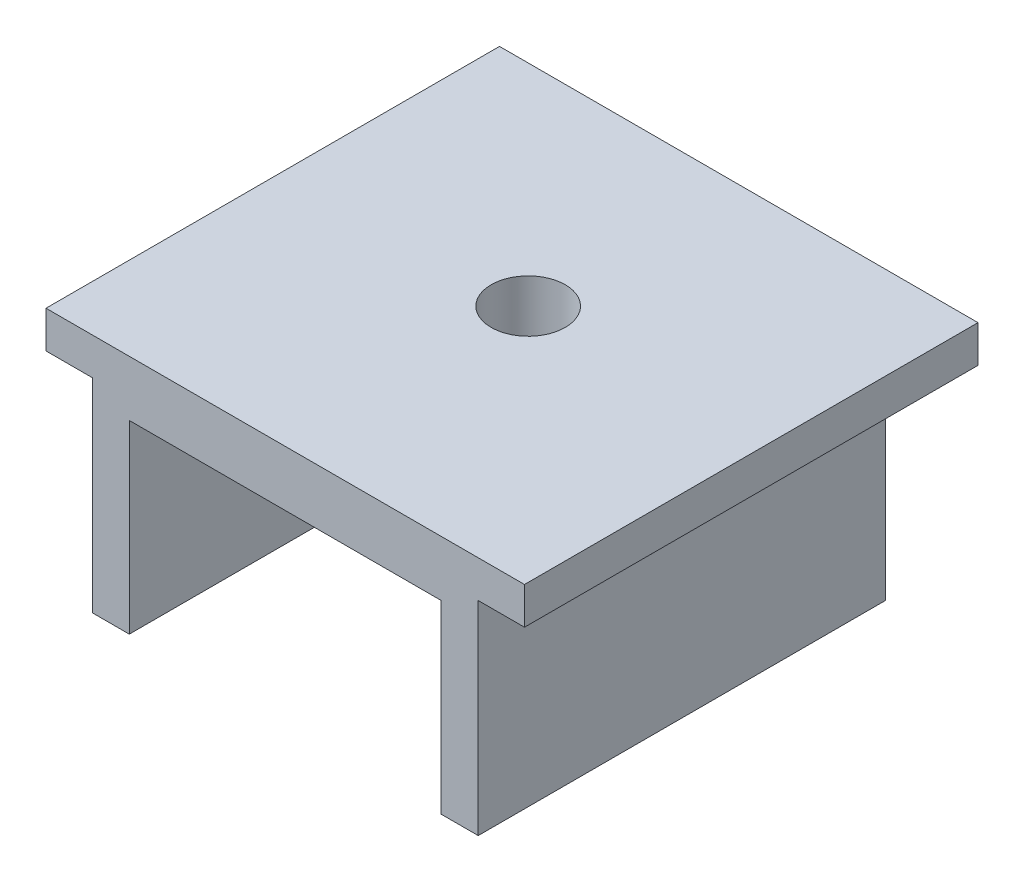
SolidWorks part; units mm, degrees
ref_plane "Front" through (0, 0, 0) normal (0, 0, 1) x (1, 0, 0)
ref_plane "Top" through (0, 0, 0) normal (0, 1, 0) x (1, 0, 0)
ref_plane "Right" through (0, 0, 0) normal (1, 0, 0) x (0, 0, -1)
sketch "草图1" plane through (0, 0, 0) normal (0, 0, 1) x (1, 0, 0)
  line L1 (20.85, -13) -> (-20.85, -13)
  line L2 (20.85, -13) -> (20.85, 13)
  line L3 (20.85, 13) -> (-20.85, 13)
  line L4 (-20.85, -13) -> (-20.85, 13)
  line L5 (20.85, -13) -> (-20.85, 13) construction
  line L6 (20.85, 13) -> (-20.85, -13) construction
  line L7 (-16.85, 7) -> (16.85, 7)
  line L8 (-16.85, 7) -> (-16.85, -13)
  line L9 (-16.85, -13) -> (16.85, -13)
  line L10 (16.85, 7) -> (16.85, -13)
  point P0 (0, 0)
  dimension "D1" = 4
  dimension "D2" = 4
  dimension "D3" = 33.7
  dimension "D4" = 6
  dimension "D5" = 26
extrude "凸台-拉伸1" add sketch "草图1" along normal blind 40 contours L7 L10 L1 L2 L3 L4 L8 region at (18.85, -12.5086, 0)
extrude "凸台-拉伸2" add sketch "草图1<3>" against normal blind 4 contours L10 L7 L8 L1 | L7 L10 L1 L2 L3 L4 L8 region at (18.85, -12.5086, 0) region at (0, -3, 0)
sketch "草图1<3>" plane through (0, 0, 0) normal (0, 0, 1) x (1, 0, 0) same geometry as "草图1"
sketch "草图2" plane through (0, 13, 0) normal (0, 1, 0) x (1, 0, 0)
  line L0 (20.85, 4) -> (-20.85, 4) construction
  line L1 (-25.85, 9) -> (25.85, 9)
  line L2 (-25.85, 9) -> (-25.85, -40)
  line L3 (-25.85, -40) -> (25.85, -40)
  line L4 (25.85, 9) -> (25.85, -40)
  line L5 (-25.85, 9) -> (25.85, -40) construction
  line L6 (-25.85, -40) -> (25.85, 9) construction
  line L7 (20.85, -40) -> (20.85, 4) construction
  line L8 (-20.85, -40) -> (-20.85, 4) construction
  line L9 (20.85, -40) -> (-20.85, -40) construction
  point P0 (0, -15.5)
  dimension "D1" = 5
  dimension "D2" = 5
  dimension "D3" = 5
  dimension "D4" = 0
extrude "凸台-拉伸3" add sketch "草图2" against normal blind 4
sketch "草图3" plane through (0, 7, 0) normal (0, -1, 0) x (1, 0, 0)
  line L0 (-16.85, 40) -> (16.85, 40) construction
  line L2 (-16.85, 0) -> (16.85, 0) construction
  circle A0 centre (0, 13.75) radius 4
  point P0 (0, 13.75)
  point P5 (0, 40)
  dimension "D3" = 8
  dimension "D1" = 13.75
  dimension "D2" = 0
extrude "切除-拉伸1" cut sketch "草图3" against normal blind 8
